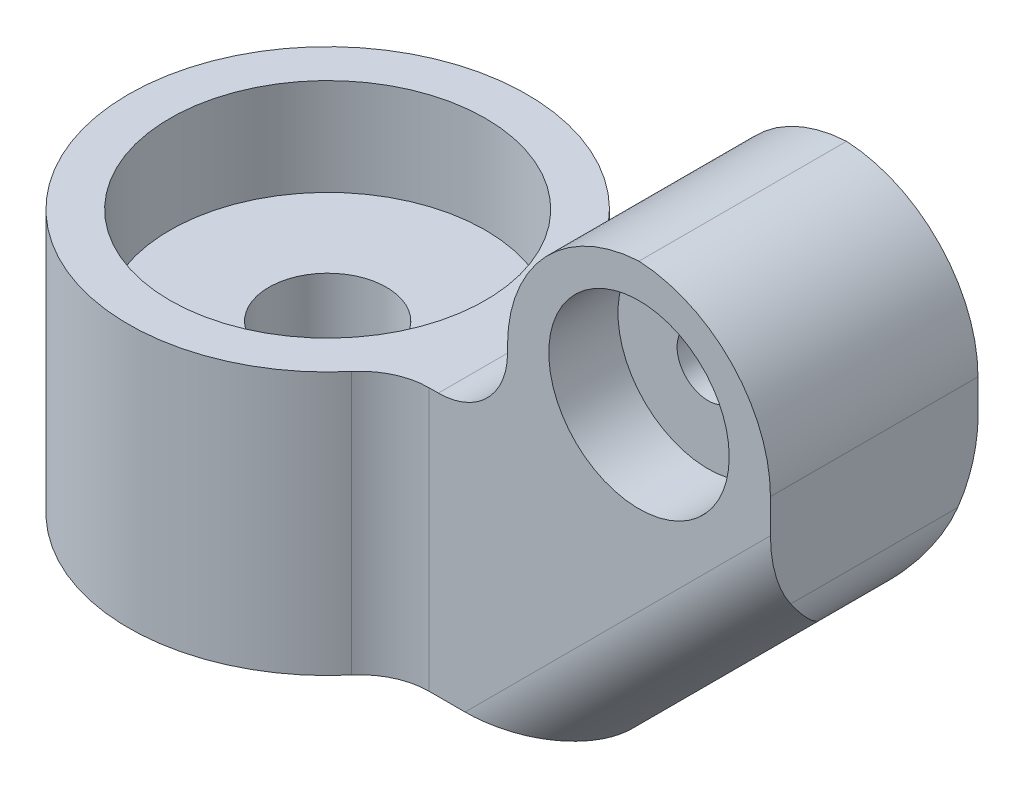
SolidWorks part; units mm, degrees
ref_plane "Front Plane" through (0, 0, 0) normal (0, 0, 1) x (1, 0, 0)
ref_plane "Top Plane" through (0, 0, 0) normal (0, 1, 0) x (1, 0, 0)
ref_plane "Right Plane" through (0, 0, 0) normal (1, 0, 0) x (0, 0, -1)
sketch "Sketch1" plane through (0, 0, 0) normal (0, 0, 1) x (1, 0, 0)
  line L0 (-9.5, 9) -> (9.5, 9)
  line L1 (9.5, 9) -> (9.5, -10.52)
  line L2 (-5.5, -25.52) -> (-30, -25.52)
  line L3 (-30, -25.52) -> (-30, -6.52)
  line L4 (-30, -6.52) -> (-9.5, -6.52)
  line L5 (-9.5, -6.52) -> (-9.5, 9)
  line L6 (-16.2026, -6.52) -> (19.4501, -6.52) construction
  line L7 (9.5, -10.52) -> (-5.5, -25.52)
  circle A0 centre (0, 0) radius 2.25
  circle A1 centre (0, 0) radius 6.52
  point P5 (9.5, -25.52)
  point P10 (0, 9)
  point P12 (0, 0)
  dimension "D1" = 4.5
  dimension "D4" = 13.04
  dimension "D2" = 19
  dimension "D3" = 9
  dimension "D5" = 30
  dimension "D7" = 19
extrude "Boss-Extrude1" add sketch "Sketch1" along normal mid plane 15 contours L6 L4 L3 L2 L1 | L5 L6 A1 L1 L0 | A1 A0 region at (-4.4799, 4.4799, 0) region at (0, 8.7547, 0) region at (-12.8509, -15.2265, 0)
extrude "Cut-Extrude1" cut sketch "Sketch1<3>" against normal blind 5 from surface contours A1 starting at face at (-9.3571, -8.0857, 7.5)
sketch "Sketch1<3>" plane through (0, 0, 0) normal (0, 0, 1) x (1, 0, 0) same geometry as "Sketch1"
extrude "Cut-Extrude2" cut sketch "Sketch1<4>" along normal blind 5 from surface contours A1 starting at face at (-9.3571, -8.0857, -7.5)
sketch "Sketch1<4>" plane through (0, 0, 0) normal (0, 0, 1) x (1, 0, 0) same geometry as "Sketch1"
sketch "Sketch2" plane through (0, -6.52, 0) normal (0, 1, 0) x (1, 0, 0)
  line L0 (-30, -7.5) -> (-30, 7.5) construction
  circle A0 centre (-30, 0) radius 11.4
  circle A1 centre (-30, 0) radius 4.25
  circle A2 centre (-30, 0) radius 14.4
  line M1 (-9.5, 7.5) -> (-30, 7.5)
  line M2 (-30, 7.5) -> (-30, -7.5)
  line M3 (-30, -7.5) -> (-9.5, -7.5)
  dimension "D1" = 22.8
  dimension "D2" = 8.5
  dimension "D3" = 3
extrude "Boss-Extrude2" add sketch "Sketch2" against normal through all contours A2
extrude "Cut-Extrude3" cut sketch "Sketch2<3>" against normal through all both and the other way through all contours A1 M2 | A1 M2 region at (-28.1962, -6.52, 0) region at (-31.8038, -6.52, 0)
sketch "Sketch2<3>" plane through (0, -6.52, 0) normal (0, 1, 0) x (1, 0, 0) same geometry as "Sketch2"
extrude "Cut-Extrude4" cut sketch "Sketch2<4>" against normal blind 7 from surface contours A1 A0 M2 M1 M3 | A1 A0 M2 M3 M1 region at (-23.9466, -6.52, 0) region at (-25.7073, -6.52, -7.8032) starting at face at (-30, -6.52, 4.25)
sketch "Sketch2<4>" plane through (0, -6.52, 0) normal (0, 1, 0) x (1, 0, 0) same geometry as "Sketch2"
extrude "Cut-Extrude5" cut sketch "Sketch2<5>" along normal blind 7 from surface contours A0 starting at face at (-30, -25.52, 4.25)
sketch "Sketch2<5>" plane through (0, -6.52, 0) normal (0, 1, 0) x (1, 0, 0) same geometry as "Sketch2"
fillet "Fillet1" radius 5 3 edges at (-17.7073, -16.02, -7.5) (-9.5, -6.52, 0) (-17.7073, -16.02, 7.5)
fillet "Fillet2" radius 10 2 edges at (-9.5, 9, 0) (9.5, 9, 0)
fillet "Fillet3" radius 5 3 edges at (2, -18.02, -7.5) (2, -18.02, 7.5) (9.5, -10.52, 0)
